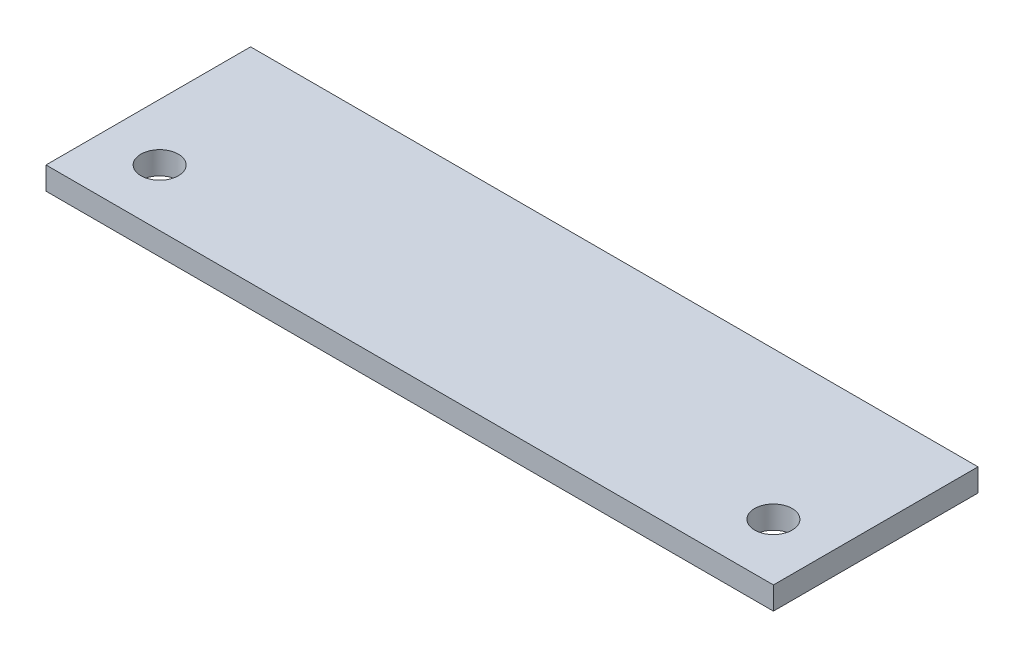
SolidWorks part; units mm, degrees
ref_plane "Front Plane" through (0, 0, 0) normal (0, 0, 1) x (1, 0, 0)
ref_plane "Top Plane" through (0, 0, 0) normal (0, 1, 0) x (1, 0, 0)
ref_plane "Right Plane" through (0, 0, 0) normal (1, 0, 0) x (0, 0, -1)
sketch "Sketch1" plane through (0, 0, 0) normal (0, 1, 0) x (1, 0, 0)
  line L1 (0, 0) -> (406.4, 0)
  line L2 (0, 0) -> (0, 114.3)
  line L3 (0, 114.3) -> (406.4, 114.3)
  line L4 (406.4, 0) -> (406.4, 114.3)
  dimension "D1" = 114.3
  dimension "D2" = 406.4
extrude "Boss-Extrude1" add sketch "Sketch1" along normal blind 12.7
sketch "Sketch2" plane through (0, 12.7, 0) normal (0, 1, 0) x (1, 0, 0)
  line L0 (0, 114.3) -> (0, 0) construction
  line L1 (0, 0) -> (406.4, 0) construction
  line L3 (203.2, 114.3) -> (203.2, 0) construction
  line L4 (406.4, 114.3) -> (0, 114.3) construction
  line L5 (0, 31.75) -> (406.4, 31.75) construction
  line L6 (406.4, 0) -> (406.4, 114.3) construction
  circle A0 centre (31.75, 31.75) radius 10.4775
  circle A1 centre (374.65, 31.75) radius 10.4775
  dimension "D1" = 31.75
  dimension "D3" = 20.955
  dimension "D2" = 31.75
extrude "Cut-Extrude1" cut sketch "Sketch2" against normal up to next
sketch3d "3DSketch1" plane through (0, 0, 0) normal (0, 0, 1) x (1, 0, 0)
  dimension "D1" = 152.4
equation "\"D3@Sketch2\"=.825"
